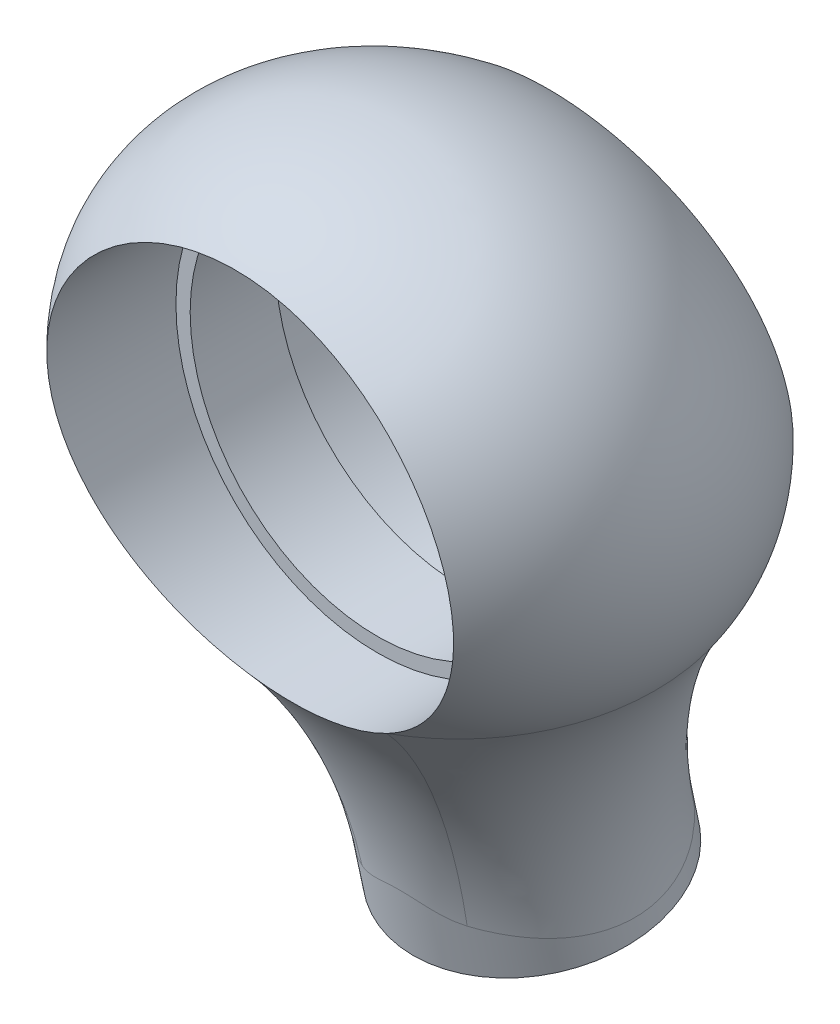
SolidWorks part; units mm, degrees
ref_plane "Front Plane" through (0, 0, 0) normal (0, 0, 1) x (1, 0, 0)
ref_plane "Top Plane" through (0, 0, 0) normal (0, 1, 0) x (1, 0, 0)
ref_plane "Right Plane" through (0, 0, 0) normal (1, 0, 0) x (0, 0, -1)
sketch "Sketch1" plane through (0, 0, 0) normal (1, 0, 0) x (0, 0, -1)
  line L0 (-32.9912, 35.941) -> (22.8888, 35.941) construction
  line L1 (22.8888, 35.941) -> (32.9912, -35.941) construction
  line L2 (32.9912, -35.941) -> (-22.8888, -35.941) construction
  line L3 (-22.8888, -35.941) -> (-32.9912, 35.941) construction
  line L4 (55, 0) -> (-55, 0) construction
  line L5 (-31.1284, -28.5735) -> (31.1284, 28.5735)
  line L6 (-32.9912, 35.941) -> (32.9912, -35.941) construction
  ellipse E0 centre (0, 0) end of major axis (32.9912, -35.941) minor radius 42.2543 (31.1284, 28.5735) -> (-31.1284, -28.5735) ccw
  point P3 (27.94, 0)
  dimension "D1" = 55.88
  dimension "D2" = 82
  dimension "D3" = 27.94
  dimension "D4" = 71.882
revolve "Revolve1" add sketch "Sketch1" angle 360 about L5
sketch "Sketch2" plane through (0, 0, 0) normal (0, 0, 1) x (1, 0, 0)
  circle A0 centre (0, 0) radius 35.941
  dimension "D1" = 71.882
extrude "Cut-Extrude1" cut sketch "Sketch2" against normal through all both and the other way through all
ref_axis "Axis1" through (-71.4316, 0, 0) along (1, 0, 0)
ref_plane "Plane1" through (0, 0, 0) normal (0, 0.9781, 0.2079) x (1, 0, 0)
ref_plane "Plane2" through (0, -49.6899, -10.5619) normal (0, 0.9781, 0.2079) x (1, 0, 0)
sketch "Sketch3" plane through (0, -49.6899, -10.5619) normal (0, 0.9781, 0.2079) x (1, 0, 0)
  line L0 (0, -50.6254) -> (0, 50.6254) construction
  line L1 (-71.4316, 0) -> (71.4316, 0) construction
  circle A0 centre (0, 2.54) radius 21.59
  circle A1 centre (0, 2.54) radius 17.145
  dimension "D1" = 34.29
  dimension "D2" = 43.18
  dimension "D3" = 2.54
extrude "Boss-Extrude1" add sketch "Sketch3" along normal up to next and the other way blind 33.02
fillet "Fillet1" radius 86.36 1 edges at (4.8514, -42.7215, 9.8304)
sketch "Sketch4" plane through (0, 0, 0) normal (1, 0, 0) x (0, 0, -1)
  line L0 (22.8888, 35.941) -> (-32.9912, 35.941) construction
  line L1 (-7.62, 35.941) -> (7.62, 35.941)
  line L2 (-7.62, 35.941) -> (-7.62, 33.401)
  line L3 (-7.62, 33.401) -> (7.62, 33.401)
  line L4 (7.62, 35.941) -> (7.62, 33.401)
  line L5 (0, 55) -> (0, -55) construction
  dimension "D1" = 15.24
  dimension "D2" = 7.62
  dimension "D3" = 2.54
revolve "Revolve2" add sketch "Sketch4" angle 360 about axis through (0, 0, -48.4066) along (0, 0, 1)
ref_plane "Plane3" through (0, 0, 0) normal (0, -0.2079, 0.9781) x (1, 0, 0)
